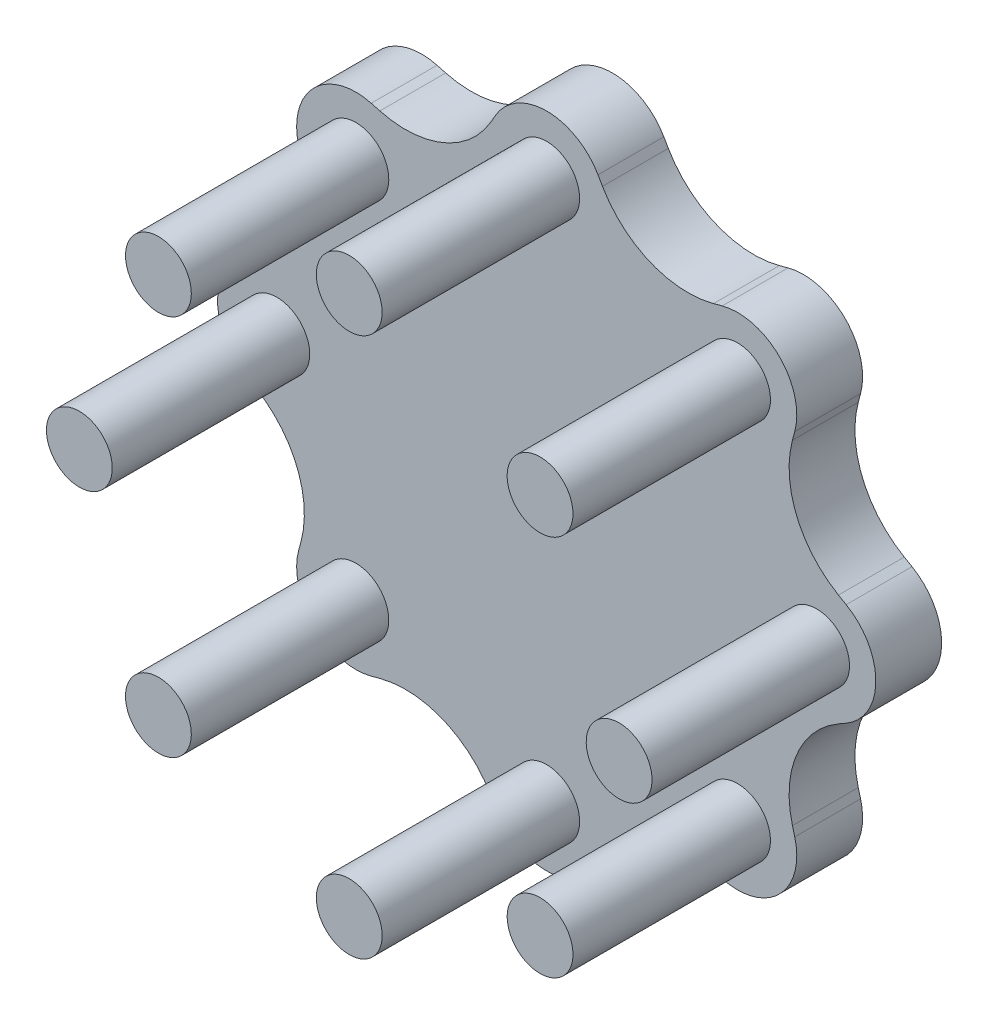
SolidWorks part; units mm, degrees
ref_plane "Front Plane" through (0, 0, 0) normal (1, 0, 0) x (0, 1, 0)
ref_plane "Top Plane" through (0, 0, 0) normal (0, 0, 1) x (0, 1, 0)
ref_plane "Right Plane" through (0, 0, 0) normal (0, 1, 0) x (-1, 0, 0)
sketch "Sketch2" plane through (0, 0, 0) normal (0, 0, 1) x (0, 1, 0)
  line L0 (-227.5, 38.9711) -> (-84.3701, 121.6072)
  line L1 (-84.3701, 121.6072) -> (-84.3701, -121.6072)
  line L2 (-84.3701, -121.6072) -> (-227.5, -38.9711)
  circle A0 centre (-205, 0) radius 25
  arc A4 (-227.5, 38.9711) -> (-227.5, -38.9711) centre (-205, 0) ccw
  point P15 (-84.3701, 0)
  dimension "D1" = 50
  dimension "D3" = 205
  dimension "D2" = 250
  dimension "D4" = 45
  dimension "D5" = 60
extrude "pinion" add sketch "Sketch2" along normal blind 200 separate body contours A0 region at (0, -205, 0)
extrude "pinion base" add sketch "Sketch2<3>" along normal blind 50 contours L2 A4 L0 L1
sketch "Sketch2<3>" plane through (0, 0, 0) normal (0, 0, 1) x (0, 1, 0) same geometry as "Sketch2"
ref_axis "Axis1" through (0, 0, 210) along (0, 0, -1)
pattern_circular "CirPattern1" count 8 over 360 about axis through (0, 0, 210) along (0, 0, -1) of bodies 103
sketch "Sketch1" plane through (0, 0, 0) normal (0, 0, 1) x (0, 1, 0)
  circle A0 centre (0, 0) radius 180
  circle A1 centre (-205, 0) radius 25 construction
extrude "Boss-Extrude1" add sketch "Sketch1" along normal blind 50
fillet "Fillet1" radius 75 8 edges at (-71.1484, -171.7674, 25) (71.1484, -171.7674, 25) (171.7674, -71.1484, 25) (171.7674, 71.1484, 25) (71.1484, 171.7674, 25) (-71.1484, 171.7674, 25) (-171.7674, 71.1484, 25) (-171.7674, -71.1484, 25)
ref_plane "Plane1" through (0, 0, 120) normal (0, 0, 1) x (0, 1, 0)
sketch "pitch" plane through (0, 0, 120) normal (0, 0, 1) x (0, 1, 0)
  circle A0 centre (0, 0) radius 205
  dimension "D1" = 410
equation "\"pinion_d\" = 50'Pinion OD"
equation "\"wheel_s\"= 500'Small Pinion Wheel OD"
equation "\"wheel_l\"= 20000'Large pinion wheel OD"
equation "\"D1@Sketch2\"=\"pinion_d\""
equation "\"D3@Sketch2\"=\"wheel_s\"/2 - \"pinion_d\"/2 - 20"
equation "\"D2@Sketch2\"=\"wheel_s\" / 2"
